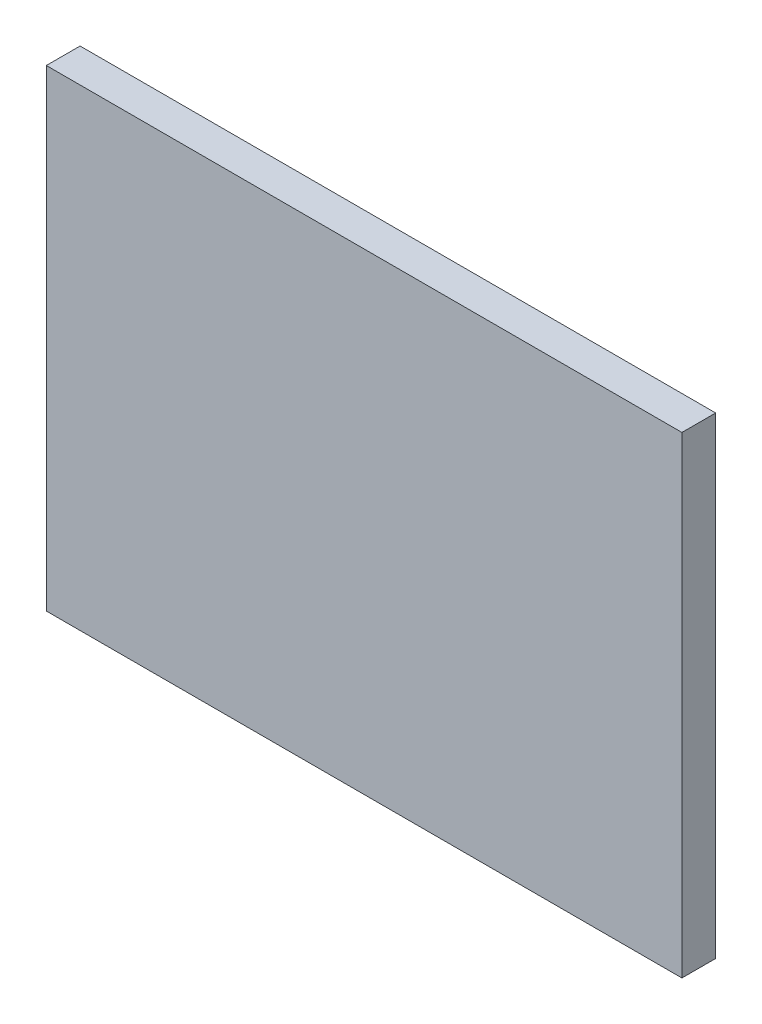
SolidWorks part; units mm, degrees
material "Pine"
ref_plane "Front Plane" through (0, 0, 0) normal (0, 0, 1) x (1, 0, 0)
ref_plane "Top Plane" through (0, 0, 0) normal (0, 1, 0) x (1, 0, 0)
ref_plane "Right Plane" through (0, 0, 0) normal (1, 0, 0) x (0, 0, -1)
sketch "Sketch1" plane through (0, 0, 0) normal (0, 0, 1) x (1, 0, 0)
  line L0 (-5300.6625, 1520.825) -> (-5451.475, 1520.825)
  line L1 (-5456.2375, 1384.3) -> (-5456.2375, 1516.0625)
  line L2 (-5557.8375, 1546.225) -> (-5194.3, 1546.225)
  line L3 (-5557.8375, 1539.875) -> (-5194.3, 1539.875)
  line L4 (-5297.4875, 1377.95) -> (-5454.65, 1377.95)
  line L5 (-5291.1375, 1384.3) -> (-5291.1375, 1516.0625)
  line L6 (-5300.6625, 1525.5875) -> (-5451.475, 1525.5875)
  line L7 (-5461, 1384.3) -> (-5461, 1516.0625)
  line L8 (-5297.4875, 1382.7125) -> (-5454.65, 1382.7125)
  line L9 (-5295.9, 1384.3) -> (-5295.9, 1516.0625)
  line L10 (-5740.4, 998.5375) -> (-5740.4, 1181.1)
  line L11 (-5740.4, 1181.1) -> (-5512.5938, 1181.1)
  line L12 (-5512.5938, 1181.1) -> (-5512.5938, 998.5375)
  line L13 (-5512.5938, 998.5375) -> (-5740.4, 998.5375)
  line L14 (-5258.5938, 1181.1) -> (-5486.4, 1181.1)
  line L15 (-5258.5938, 998.5375) -> (-5258.5938, 1181.1)
  line L16 (-5486.4, 998.5375) -> (-5258.5938, 998.5375)
  line L17 (-5486.4, 1181.1) -> (-5486.4, 998.5375)
  line L18 (-5740.4, 898.525) -> (-5011.7375, 898.525)
  line L19 (-5168.1062, 1384.3) -> (-5168.1062, 1392.2375)
  line L20 (-5176.0437, 1400.175) -> (-5245.8937, 1400.175)
  line L21 (-5253.8313, 1392.2375) -> (-5253.8313, 1384.3)
  line L22 (-5451.475, 1512.8875) -> (-5451.475, 1384.3)
  line L23 (-5303.8375, 1516.0625) -> (-5448.3, 1516.0625)
  line L24 (-5498.3062, 1384.3) -> (-5451.475, 1384.3)
  line L25 (-5253.8313, 1384.3) -> (-5300.6625, 1384.3)
  line L26 (-5584.0312, 1384.3) -> (-5740.4, 1384.3)
  line L27 (-5564.1875, 1536.7) -> (-5740.4, 1536.7)
  line L28 (-5740.4, 1357.3125) -> (-5740.4, 1206.5)
  line L29 (-5011.7375, 1357.3125) -> (-5740.4, 1357.3125)
  line L30 (-5011.7375, 1206.5) -> (-5011.7375, 1357.3125)
  line L31 (-5740.4, 1206.5) -> (-5011.7375, 1206.5)
  line L32 (-4765.675, 1549.4) -> (-4978.4, 1549.4)
  line L33 (-4765.675, 1397) -> (-4765.675, 1549.4)
  line L34 (-4978.4, 1397) -> (-4765.675, 1397)
  line L35 (-4978.4, 1549.4) -> (-4978.4, 1397)
  line L36 (-4765.675, 1371.6) -> (-4978.4, 1371.6)
  line L37 (-4765.675, 1219.2) -> (-4765.675, 1371.6)
  line L38 (-4978.4, 1219.2) -> (-4765.675, 1219.2)
  line L39 (-4978.4, 1371.6) -> (-4978.4, 1219.2)
  line L40 (-5284.7875, 803.275) -> (-5272.0875, 803.275)
  line L41 (-5187.95, 1536.7) -> (-5011.7375, 1536.7)
  line L42 (-5300.6625, 1384.3) -> (-5300.6625, 1512.8875)
  line L43 (-5740.4, 1536.7) -> (-5740.4, 1384.3)
  line L44 (-5557.8375, 1536.7) -> (-5557.8375, 1549.4)
  line L45 (-5557.8375, 1549.4) -> (-5194.3, 1549.4)
  line L46 (-5194.3, 1549.4) -> (-5194.3, 1536.7)
  line L47 (-5011.7375, 1536.7) -> (-5011.7375, 1384.3)
  line L48 (-5011.7375, 1384.3) -> (-5168.1062, 1384.3)
  line L49 (-5498.3062, 1384.3) -> (-5498.3062, 1392.2375)
  line L50 (-5506.2437, 1400.175) -> (-5576.0938, 1400.175)
  line L51 (-5584.0312, 1392.2375) -> (-5584.0312, 1384.3)
  line L52 (-5740.4, 660.4) -> (-5740.4, 898.525)
  line L53 (-5011.7375, 898.525) -> (-5011.7375, 660.4)
  line L54 (-5011.7375, 660.4) -> (-5740.4, 660.4)
  line L55 (-5291.1375, 803.275) -> (-5291.1375, 752.475)
  line L56 (-5265.7375, 752.475) -> (-5265.7375, 803.275)
  line L57 (-5284.7875, 752.475) -> (-5272.0875, 752.475)
  arc A0 (-5451.475, 1520.825) -> (-5456.2375, 1516.0625) centre (-5451.475, 1516.0625) ccw
  arc A1 (-5461, 1384.3) -> (-5454.65, 1377.95) centre (-5454.65, 1384.3) ccw
  arc A2 (-5297.4875, 1377.95) -> (-5291.1375, 1384.3) centre (-5297.4875, 1384.3) ccw
  circle A3 centre (-5037.9312, 1233.4875) radius 1.5875
  circle A4 centre (-5037.9312, 1328.7375) radius 1.5875
  circle A5 centre (-5714.2063, 1233.4875) radius 1.5875
  circle A6 centre (-5714.2063, 1328.7375) radius 1.5875
  circle A7 centre (-5018.0875, 1333.5) radius 1.5875
  circle A8 centre (-5018.0875, 1231.9) radius 1.5875
  circle A9 centre (-5734.05, 1231.9) radius 1.5875
  circle A10 centre (-5734.05, 1333.5) radius 1.5875
  circle A11 centre (-5734.05, 1511.3) radius 1.5875
  circle A12 centre (-5734.05, 1409.7) radius 1.5875
  circle A13 centre (-5018.0875, 1511.3) radius 1.5875
  circle A14 centre (-5018.0875, 1409.7) radius 1.5875
  arc A15 (-5557.8375, 1546.225) -> (-5557.8375, 1539.875) centre (-5557.8375, 1543.05) ccw
  arc A16 (-5194.3, 1539.875) -> (-5194.3, 1546.225) centre (-5194.3, 1543.05) ccw
  arc A17 (-5291.1375, 1516.0625) -> (-5300.6625, 1525.5875) centre (-5300.6625, 1516.0625) ccw
  arc A18 (-5451.475, 1525.5875) -> (-5461, 1516.0625) centre (-5451.475, 1516.0625) ccw
  arc A19 (-5456.2375, 1384.3) -> (-5454.65, 1382.7125) centre (-5454.65, 1384.3) ccw
  arc A20 (-5297.4875, 1382.7125) -> (-5295.9, 1384.3) centre (-5297.4875, 1384.3) ccw
  arc A21 (-5295.9, 1516.0625) -> (-5300.6625, 1520.825) centre (-5300.6625, 1516.0625) ccw
  circle A22 centre (-5702.3, 892.175) radius 1.5875
  circle A23 centre (-5734.05, 860.425) radius 1.5875
  circle A24 centre (-5474.8906, 892.175) radius 1.5875
  circle A25 centre (-5277.2469, 892.175) radius 1.5875
  circle A26 centre (-5049.8375, 892.175) radius 1.5875
  circle A27 centre (-5018.0875, 860.425) radius 1.5875
  circle A28 centre (-5296.6938, 1174.75) radius 1.5875
  circle A29 centre (-5448.3, 1174.75) radius 1.5875
  circle A30 centre (-5264.9437, 1155.7) radius 1.5875
  circle A31 centre (-5264.9437, 1023.9375) radius 1.5875
  circle A32 centre (-5518.9438, 1155.7) radius 1.5875
  circle A33 centre (-5518.9438, 1023.9375) radius 1.5875
  circle A34 centre (-5702.3, 1004.8875) radius 1.5875
  circle A35 centre (-5550.6937, 1004.8875) radius 1.5875
  arc A36 (-5576.0938, 1400.175) -> (-5584.0312, 1392.2375) centre (-5576.0938, 1392.2375) ccw
  arc A37 (-5168.1062, 1392.2375) -> (-5176.0437, 1400.175) centre (-5176.0437, 1392.2375) ccw
  arc A38 (-5245.8937, 1400.175) -> (-5253.8313, 1392.2375) centre (-5245.8937, 1392.2375) ccw
  arc A39 (-5448.3, 1516.0625) -> (-5451.475, 1512.8875) centre (-5448.3, 1512.8875) ccw
  arc A40 (-5284.7875, 803.275) -> (-5291.1375, 803.275) centre (-5287.9625, 803.275) ccw
  circle A41 centre (-5679.2812, 1026.3187) radius 1.5875
  circle A42 centre (-5679.2812, 1153.3187) radius 1.5875
  circle A43 centre (-5571.3313, 1153.3187) radius 1.5875
  circle A44 centre (-5571.3313, 1026.3187) radius 1.5875
  circle A45 centre (-5317.3312, 1153.3187) radius 1.5875
  circle A46 centre (-5317.3312, 1026.3187) radius 1.5875
  circle A47 centre (-5425.2812, 1026.3187) radius 1.5875
  circle A48 centre (-5425.2812, 1153.3187) radius 1.5875
  arc A49 (-5194.3, 1536.7) -> (-5187.95, 1536.7) centre (-5191.125, 1536.7) ccw
  arc A50 (-5564.1875, 1536.7) -> (-5557.8375, 1536.7) centre (-5561.0125, 1536.7) ccw
  arc A51 (-5300.6625, 1512.8875) -> (-5303.8375, 1516.0625) centre (-5303.8375, 1512.8875) ccw
  arc A52 (-5498.3062, 1392.2375) -> (-5506.2437, 1400.175) centre (-5506.2437, 1392.2375) ccw
  circle A53 centre (-5712.46, 784.225) radius 4.7625
  arc A54 (-5272.0875, 752.475) -> (-5265.7375, 752.475) centre (-5268.9125, 752.475) ccw
  arc A55 (-5291.1375, 752.475) -> (-5284.7875, 752.475) centre (-5287.9625, 752.475) ccw
  circle A56 centre (-5182.3938, 684.2125) radius 3.175
  circle A57 centre (-5239.5437, 684.2125) radius 3.175
  circle A58 centre (-5512.5938, 684.2125) radius 3.175
  circle A59 centre (-5569.7437, 684.2125) radius 3.175
  circle A60 centre (-5474.8906, 666.75) radius 1.5875
  circle A61 centre (-5277.2469, 666.75) radius 1.5875
  circle A62 centre (-5734.05, 698.5) radius 1.5875
  circle A63 centre (-5702.3, 666.75) radius 1.5875
  circle A64 centre (-5049.8375, 666.75) radius 1.5875
  circle A65 centre (-5018.0875, 698.5) radius 1.5875
  circle A66 centre (-5713.73, 835.025) radius 4.7625
  circle A67 centre (-5712.46, 819.785) radius 4.7625
  circle A68 centre (-5712.46, 802.005) radius 4.7625
  circle A69 centre (-5714.2063, 1314.45) radius 3.175
  circle A70 centre (-5037.9312, 1314.45) radius 3.175
  arc A71 (-5265.7375, 803.275) -> (-5272.0875, 803.275) centre (-5268.9125, 803.275) ccw
  ellipse E0 centre (-5371.3062, 1089.8188) end of major axis (-5277.6438, 1089.8188) minor radius 65.0875
  ellipse E1 centre (-5625.3062, 1089.8188) end of major axis (-5531.6438, 1089.8188) minor radius 65.0875
sketch "SideOutline" plane through (0, 0, 0) normal (0, 0, 1) x (1, 0, 0)
  line L0 (-4763.135, 1379.22) -> (-4763.135, 1219.2)
  line L1 (-4763.135, 1219.2) -> (-4978.4, 1219.2)
  line L2 (-4978.4, 1219.2) -> (-4978.4, 1379.22)
  line L3 (-4978.4, 1379.22) -> (-4763.135, 1379.22)
  line L4 (-4870.7675, 1379.22) -> (-4870.7675, 1219.2) construction
  line L5 (-4870.7675, 1299.21) -> (-4978.4, 1299.21) construction
  line L6 (-4870.7675, 1299.21) -> (-4763.135, 1299.21) construction
extrude "SideOutline_Thickness" add sketch "SideOutline" against normal blind 11.43
